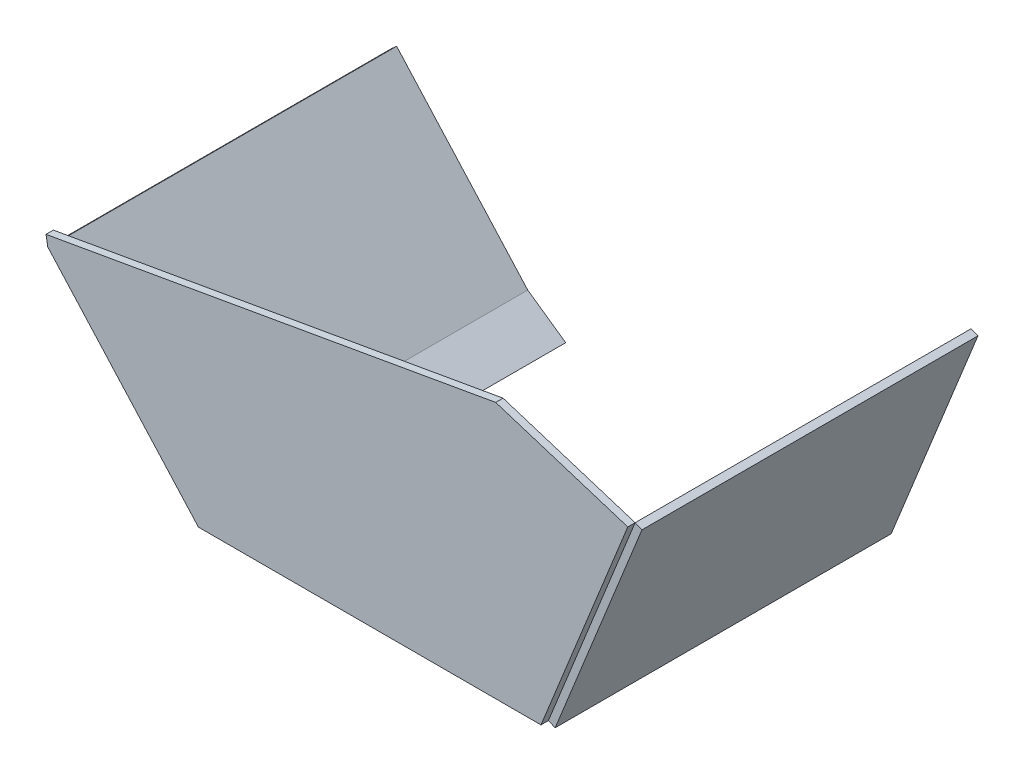
SolidWorks part; units mm, degrees
ref_plane "Front Plane" through (0, 0, 0) normal (0, 0, 1) x (1, 0, 0)
ref_plane "Top Plane" through (0, 0, 0) normal (0, 1, 0) x (1, 0, 0)
ref_plane "Right Plane" through (0, 0, 0) normal (1, 0, 0) x (0, 0, -1)
ref_axis "Axis1" through (0, 0, -14.8175) along (0, 0, 1)
sketch "Sketch1" plane through (0, 0, 0) normal (0, 0, 1) x (1, 0, 0)
  line L0 (-143.554, 0) -> (143.554, 0) construction
  line L1 (-164.2121, 22.9431) -> (-277.3802, 148.629)
  line L4 (-152.0988, 0) -> (-282.0991, 144.38)
  line L5 (-282.0991, 144.38) -> (-277.3802, 148.629)
  line L9 (-131.446, 0) -> (-164.2121, 22.9431)
  line L10 (-131.446, 0) -> (-152.0988, 0)
  line L11 (-164.2121, 22.9431) -> (-143.554, 0) construction
  line L12 (143.554, 0) -> (218.4753, 185.4368) construction
  line L13 (143.554, 0) -> (149.4416, -2.3788)
  line L14 (149.4416, -2.3788) -> (224.363, 183.058)
  line L15 (224.363, 183.058) -> (218.4753, 185.4368)
  line L16 (218.4753, 185.4368) -> (143.554, 0)
  point P4 (0, 0)
  point P13 (143.554, 0)
  point P14 (218.4753, 185.4368)
  dimension "D1" = 48
  dimension "D2" = 35
  dimension "D3" = 275
  dimension "D4" = 200
  dimension "D5" = 40
  dimension "D6" = 6.35
  dimension "D7" = 68
  dimension "D8" = 200
  dimension "D9" = 6.35
extrude "Boss-Extrude1" add sketch "Sketch1" along normal blind 290
sketch "Sketch2" plane through (0, 0, 290) normal (0, 0, 1) x (1, 0, 0)
  line L0 (-152.0988, 0) -> (-282.0991, 144.38)
  line L1 (-283.632, 153.0733) -> (104.4957, 221.5107)
  line L3 (143.554, 0) -> (-152.0988, 0)
  line L4 (-282.0991, 144.38) -> (-152.0988, 0) construction
  line L5 (143.554, 0) -> (218.4753, 185.4368)
  line L7 (-282.0991, 144.38) -> (-283.632, 153.0733)
  line L8 (-277.3802, 148.629) -> (-282.0991, 144.38) construction
  line L9 (218.4753, 185.4368) -> (104.4957, 221.5107)
  line L10 (143.554, 0) -> (104.4957, 221.5107) construction
  line L11 (-152.0988, 0) -> (-131.446, 0) construction
  dimension "D1" = 10
  dimension "D2" = 200
  dimension "D3" = 275
extrude "Boss-Extrude2" add sketch "Sketch2" along normal blind 6.35
ref_plane "Plane1" through (0, 0, 0) normal (0.9848, 0.1736, 0) x (0, 0, 1)
